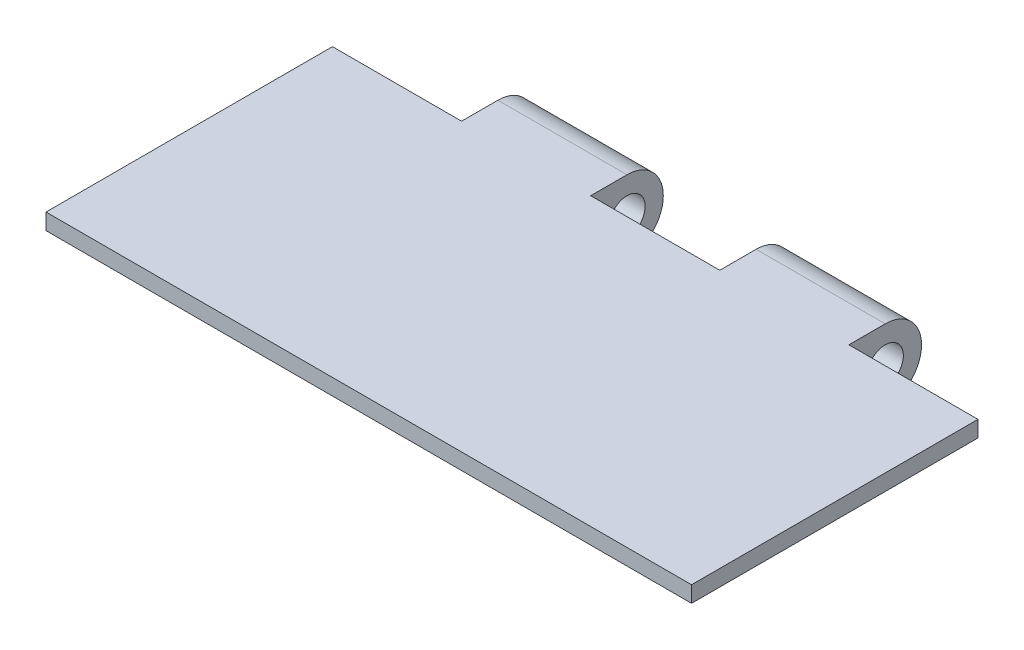
SolidWorks part; units mm, degrees
material "Brass"
ref_plane "Front Plane" through (0, 0, 0) normal (0, 0, 1) x (1, 0, 0)
ref_plane "Top Plane" through (0, 0, 0) normal (0, 1, 0) x (1, 0, 0)
ref_plane "Right Plane" through (0, 0, 0) normal (1, 0, 0) x (0, 0, -1)
sketch "Sketch1" plane through (0, 0, 0) normal (0, 1, 0) x (1, 0, 0)
  line L0 (12.8491, 13.3832) -> (7.7691, 13.3832)
  line L1 (23.0091, 13.3832) -> (17.9291, 13.3832)
  line L2 (28.0891, 10.5257) -> (28.0891, -0.7455)
  line L3 (28.0891, -0.7455) -> (2.6891, -0.7455)
  line L4 (2.6891, 10.5257) -> (2.6891, -0.7455)
  line L7 (2.6891, 10.5257) -> (7.7691, 10.5257)
  line L8 (7.7691, 13.3832) -> (7.7691, 10.5257)
  line L11 (28.0891, 10.5257) -> (23.0091, 10.5257)
  line L12 (23.0091, 13.3832) -> (23.0091, 10.5257)
  line L14 (12.8491, 13.3832) -> (12.8491, 10.5257)
  line L15 (12.8491, 10.5257) -> (17.9291, 10.5257)
  line L16 (17.9291, 13.3832) -> (17.9291, 10.5257)
  dimension "D7" = 5.08
  dimension "D1" = 2.8575
  dimension "D2" = 14.1288
  dimension "D3" = 5.08
  dimension "D4" = 25.4
  dimension "D5" = 5.08
  dimension "D6" = 5.08
  dimension "D9" = 2.8575
extrude "Boss-Extrude1" add sketch "Sketch1" along normal blind 0.635
sketch "Sketch2" plane through (0, 0.635, 0) normal (0, 1, 0) x (1, 0, 0)
  line L1 (12.8491, 13.3832) -> (7.7691, 13.3832)
  line L2 (12.8491, 13.3832) -> (12.8491, 10.5257)
  line L3 (12.8491, 10.5257) -> (7.7691, 10.5257)
  line L4 (7.7691, 13.3832) -> (7.7691, 10.5257)
  line L5 (17.9291, 13.3832) -> (23.0091, 13.3832)
  line L6 (17.9291, 13.3832) -> (17.9291, 10.5257)
  line L7 (17.9291, 10.5257) -> (23.0091, 10.5257)
  line L8 (23.0091, 13.3832) -> (23.0091, 10.5257)
extrude "Boss-Extrude2" add sketch "Sketch2" against normal blind 2.8575
fillet "Fillet1" radius 1.4287 6 edges at (10.3091, -2.2225, -10.5257) (20.4691, -2.2225, -10.5257) (20.4691, -2.2225, -13.3832) (10.3091, -2.2225, -13.3832) (10.3091, 0.635, -13.3832) (20.4691, 0.635, -13.3832)
sketch "Sketch3" plane through (23.0091, 0, 0) normal (1, 0, 0) x (0, 0, -1)
  circle A0 centre (11.9545, -0.7937) radius 0.7144
  dimension "D1" = 1.4287
extrude "Cut-Extrude1" cut sketch "Sketch3" against normal blind 30
